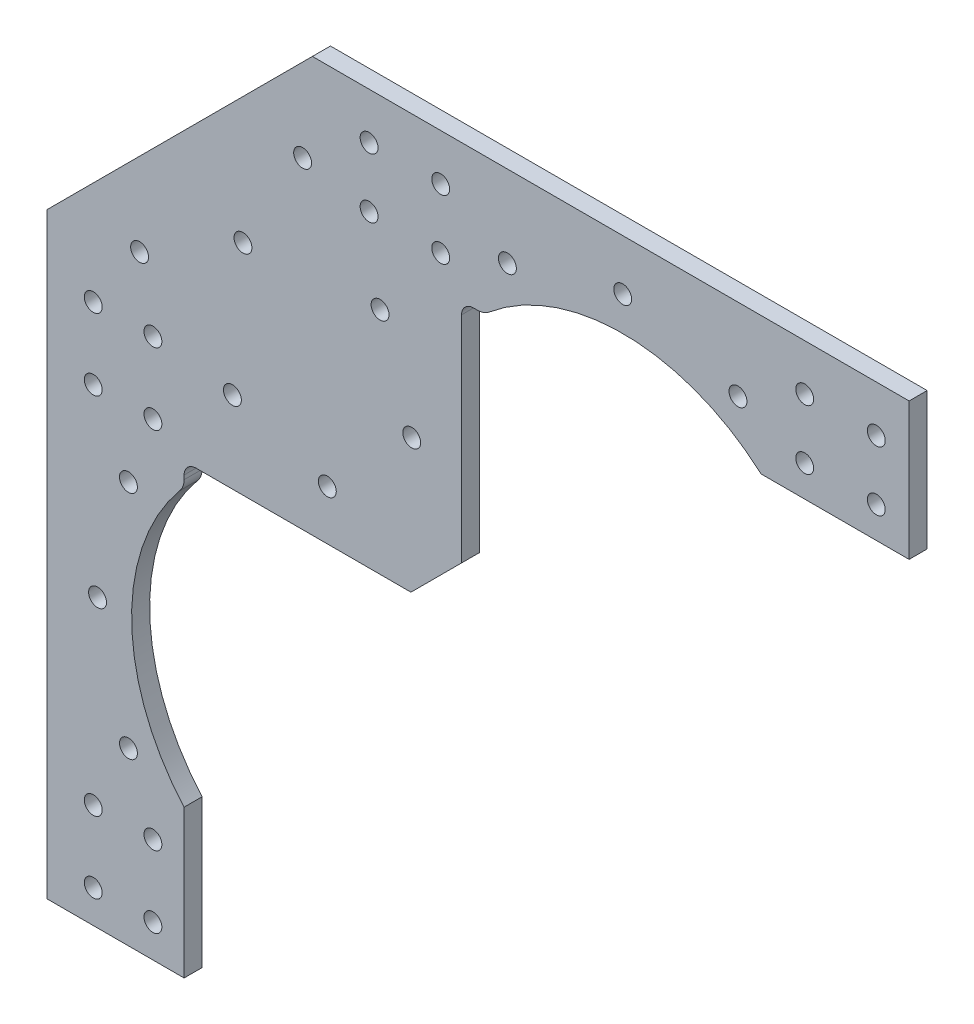
SolidWorks part; units mm, degrees
ref_plane "Front Plane" through (0, 0, 0) normal (0, 0, 1) x (1, 0, 0)
ref_plane "Top Plane" through (0, 0, 0) normal (0, 1, 0) x (1, 0, 0)
ref_plane "Right Plane" through (0, 0, 0) normal (1, 0, 0) x (0, 0, -1)
sketch "Sketch1" plane through (0, 0, 0) normal (0, 0, 1) x (1, 0, 0)
  line L0 (0, 0) -> (0, 73.5) construction
  line L1 (-96.5, -48) -> (-73.5, -48)
  line L2 (-96.5, -48) -> (-96.5, 52)
  line L4 (-73.5, -48) -> (-73.5, 27) construction
  line L5 (-52, 96.5) -> (48, 96.5)
  line L7 (-27, 73.5) -> (48, 73.5) construction
  line L8 (48, 96.5) -> (48, 73.5)
  line L9 (0, 0) -> (-73.5, 0) construction
  line L10 (-27, 73.5) -> (-73.5, 27) construction
  line L11 (-73.5, 73.5) -> (-27, 73.5) construction
  line L12 (-73.5, 27) -> (-73.5, 73.5) construction
  line L13 (-52, 96.5) -> (-96.5, 52)
  line L14 (-96.5, 96.5) -> (-52, 96.5) construction
  line L15 (-96.5, 52) -> (-96.5, 96.5) construction
  line L16 (-24.3179, 73.5) -> (-25, 73.5)
  line L17 (23.2069, 73.5) -> (48, 73.5)
  line L18 (-73.5, 25) -> (-73.5, 24.3179)
  line L19 (-73.5, -48) -> (-73.5, -23.2069)
  line L20 (-73.5, 23.2069) -> (-73.5, -23.2069) construction
  line L21 (-23.2069, 73.5) -> (23.2069, 73.5) construction
  line L22 (-71.5, 27) -> (-35.4853, 27)
  line L23 (-27, 35.4853) -> (-27, 71.5)
  line L24 (-35.4853, 27) -> (-27, 35.4853)
  line L25 (-25, 73.5) -> (-27, 73.5) construction
  line L26 (-27, 71.5) -> (-27, 73.5) construction
  line L27 (-73.5, 27) -> (-73.5, 25) construction
  line L28 (-73.5, 27) -> (-71.5, 27) construction
  line L29 (-23.2069, 73.5) -> (-24.3179, 73.5) construction
  line L30 (-73.5, 24.3179) -> (-73.5, 23.2069) construction
  arc A0 (23.2069, 73.5) -> (-22.3981, 74.1947) centre (0, 47.3) ccw
  arc A1 (-74.1947, 22.3981) -> (-73.5, -23.2069) centre (-47.3, 0) ccw
  arc A2 (-25, 73.5) -> (-27, 71.5) centre (-25, 71.5) ccw
  arc A3 (-71.5, 27) -> (-73.5, 25) centre (-71.5, 25) ccw
  arc A4 (-24.3179, 73.5) -> (-22.3981, 74.1947) centre (-24.3179, 76.5) ccw
  arc A5 (-22.3981, 74.1947) -> (-23.2069, 73.5) centre (0, 47.3) ccw construction
  arc A6 (-73.5, 24.3179) -> (-74.1947, 22.3981) centre (-76.5, 24.3179) cw
  arc A7 (-73.5, 23.2069) -> (-74.1947, 22.3981) centre (-47.3, 0) ccw construction
  dimension "D6" = 35
  dimension "D10" = 2
  dimension "D11" = 3
  dimension "D1" = 135
  dimension "D2" = 23
  dimension "D3" = 73.5
  dimension "D4" = 48
  dimension "D8" = 27
  dimension "D9" = 12
  dimension "D5" = 100
  dimension "D7" = 26.2
extrude "Boss-Extrude1" add sketch "Sketch1" along normal blind 3.0226
ref_axis "Axis1" through (0, 0, -0.2) along (0, 0, 1)
sketch "Sketch3" plane through (0, 0, 3.0226) normal (0, 0, 1) x (1, 0, 0)
  line L1 (30.5, 88.7259) -> (30.5, 78.7259) construction
  line L2 (30.5, 88.7259) -> (42.5, 88.7259) construction
  line L3 (42.5, 88.7259) -> (42.5, 78.7259) construction
  line L4 (30.5, 78.7259) -> (42.5, 78.7259) construction
  line L16 (-30.5, 78.7259) -> (0, 78.7259) construction
  line L17 (0, 78.7259) -> (0, 0) construction
  line L18 (0, 78.7259) -> (30.5, 78.7259) construction
  line L19 (-78.7259, 0) -> (0, 0) construction
  line L20 (-78.7259, -30.5) -> (-78.7259, 0) construction
  line L21 (-78.7259, 0) -> (-78.7259, 30.5) construction
  line L30 (-42.5, 88.7259) -> (-42.5, 78.7259) construction
  line L31 (-42.5, 88.7259) -> (-30.5, 88.7259) construction
  line L32 (-30.5, 88.7259) -> (-30.5, 78.7259) construction
  line L33 (-42.5, 78.7259) -> (-30.5, 78.7259) construction
  line L34 (-88.7259, 42.5) -> (-88.7259, 30.5) construction
  line L35 (-88.7259, 42.5) -> (-78.7259, 42.5) construction
  line L36 (-78.7259, 42.5) -> (-78.7259, 30.5) construction
  line L37 (-88.7259, 30.5) -> (-78.7259, 30.5) construction
  line L38 (-88.7259, -30.5) -> (-88.7259, -42.5) construction
  line L39 (-88.7259, -30.5) -> (-78.7259, -30.5) construction
  line L40 (-78.7259, -30.5) -> (-78.7259, -42.5) construction
  line L41 (-88.7259, -42.5) -> (-78.7259, -42.5) construction
  circle A0 centre (30.5, 78.7259) radius 1.5
  circle A1 centre (30.5, 88.7259) radius 1.5
  circle A2 centre (42.5, 88.7259) radius 1.5
  circle A3 centre (42.5, 78.7259) radius 1.5
  circle A24 centre (-42.5, 78.7259) radius 1.5
  circle A25 centre (-42.5, 88.7259) radius 1.5
  circle A26 centre (-30.5, 88.7259) radius 1.5
  circle A27 centre (-30.5, 78.7259) radius 1.5
  circle A28 centre (-88.7259, 30.5) radius 1.5
  circle A29 centre (-88.7259, 42.5) radius 1.5
  circle A30 centre (-78.7259, 42.5) radius 1.5
  circle A31 centre (-78.7259, 30.5) radius 1.5
  circle A32 centre (-88.7259, -42.5) radius 1.5
  circle A33 centre (-88.7259, -30.5) radius 1.5
  circle A34 centre (-78.7259, -30.5) radius 1.5
  circle A35 centre (-78.7259, -42.5) radius 1.5
  dimension "D1" = 3
  dimension "D8" = 30.5
  dimension "D2" = 12
  dimension "D6" = 10
  dimension "D3" = 78.7259
extrude "Cut-Extrude1" cut sketch "Sketch3" against normal blind 10
sketch "Sketch4" plane through (0, 0, 3.0226) normal (0, 0, 1) x (1, 0, 0)
  line L0 (0, 0) -> (0, 88) construction
  line L1 (0, 0) -> (-63.6396, 63.6396) construction
  line L2 (0, 0) -> (-88, 0) construction
  line L3 (-82.8236, 19.3185) -> (-88, 0) construction
  line L4 (-88, 0) -> (-82.8236, -19.3185) construction
  line L5 (-80.9601, 53.6396) -> (-63.6396, 63.6396) construction
  line L6 (-63.6396, 63.6396) -> (-83.2677, 83.2677) construction
  line L7 (-19.3185, 82.8236) -> (0, 88) construction
  line L8 (-65.4074, 40.6586) -> (-40.6586, 65.4074) construction
  line L9 (-35.3553, 49.4975) -> (-49.4975, 35.3553) construction
  line L10 (-73.5, -48) -> (-73.5, -23.2069) construction
  line L11 (-35.4853, 27) -> (-27, 35.4853) construction
  circle A0 centre (-88, 0) radius 1.5
  circle A1 centre (-63.6396, 63.6396) radius 1.5
  circle A2 centre (0, 88) radius 1.5
  circle A3 centre (-80.9601, 53.6396) radius 1.5
  circle A4 centre (-53.6396, 80.9601) radius 1.5
  circle A5 centre (19.3185, 82.8236) radius 1.5
  circle A6 centre (-19.3185, 82.8236) radius 1.5
  circle A7 centre (-82.8236, 19.3185) radius 1.5
  circle A8 centre (-82.8236, -19.3185) radius 1.5
  circle A9 centre (-40.6586, 65.4074) radius 1.5
  circle A10 centre (-65.4074, 40.6586) radius 1.5
  circle A11 centre (-49.4975, 35.3553) radius 1.5
  circle A12 centre (-35.3553, 49.4975) radius 1.5
  dimension "D2" = 3
  dimension "D1" = 45
  dimension "D3" = 14.5
  dimension "D4" = 75
  dimension "D5" = 20
  dimension "D6" = 45.8162
  dimension "D7" = 75
  dimension "D8" = 75
  dimension "D9" = 35
  dimension "D10" = 20
  dimension "D11" = 15
  dimension "D12" = 15
extrude "Cut-Extrude2" cut sketch "Sketch4" against normal through all
equation "\"EyeDiameter\" = 35"
equation "\"BasePlaneDistance\" = \"EyeDiameter\"/2+19.84"
equation "\"EyeClearance\" = 2"
equation "\"L2Thickness\" = 8"
equation "\"L2_ID\" = 20"
equation "\"Offset\"= - 2"
equation "\"D3@Sketch1\"=\"BasePlaneDistance\" + 38.16 +\"Offset\""
equation "\"D3@Sketch3\"=\"BasePlaneDistance\" - 37.34+78.72592343"
equation "\"D7@Sketch1\"=24.20 - \"Offset\""
equation "\"D2@Sketch1\"=25.00 + \"Offset\""
